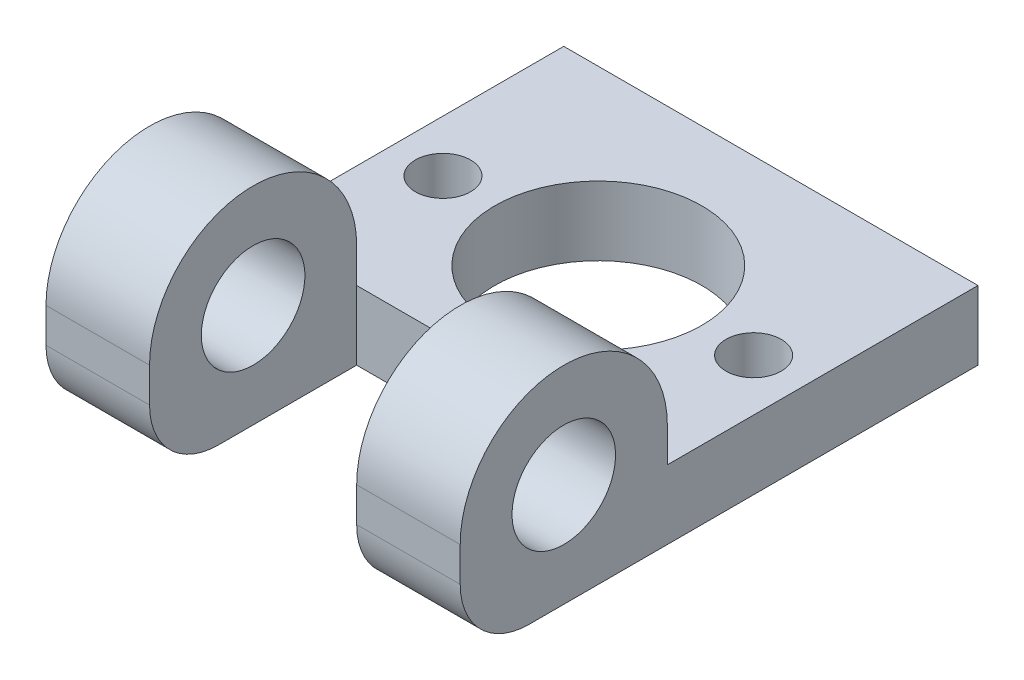
SolidWorks part; units mm, degrees
ref_plane "前视基准面" through (0, 0, 0) normal (0, 0, 1) x (1, 0, 0)
ref_plane "上视基准面" through (0, 0, 0) normal (0, 1, 0) x (1, 0, 0)
ref_plane "右视基准面" through (0, 0, 0) normal (1, 0, 0) x (0, 0, -1)
sketch "草图1" plane through (0, 0, 0) normal (0, 1, 0) x (1, 0, 0)
  line L0 (-4.5, 2.5) -> (4.5, 2.5) construction
  line L1 (6, -7.5) -> (-6, -7.5)
  line L2 (6, -7.5) -> (6, 7.5)
  line L3 (6, 7.5) -> (-6, 7.5)
  line L4 (-6, -7.5) -> (-6, 7.5)
  line L5 (0, 7.5) -> (0, -7.5) construction
  line L6 (6, 0) -> (-6, 0) construction
  line L7 (0, 2.5) -> (0, 7.5) construction
  circle A0 centre (-4.5, 2.5) radius 0.8
  circle A1 centre (4.5, 2.5) radius 0.8
  circle A2 centre (0, 2.5) radius 3
  point P0 (0, 0)
  dimension "D3" = 9
  dimension "D4" = 1.6
  dimension "D5" = 5
  dimension "D6" = 6
  dimension "D1" = 12
  dimension "D2" = 15
extrude "凸台-拉伸1" add sketch "草图1" along normal blind 2
sketch "草图2" plane through (-6, 0, 0) normal (-1, 0, 0) x (0, 0, 1)
  line L1 (1.5, 3) -> (1.5, 2)
  line L2 (-7.5, 2) -> (7.5, 2) construction
  line L3 (7.5, 2) -> (7.5, 3)
  line L4 (-7.5, 0) -> (7.5, 0) construction
  arc A0 (7.5, 3) -> (1.5, 3) centre (4.5, 3) ccw
  circle A1 centre (4.5, 3) radius 1.5
  line M3 (7.5, 2) -> (-7.5, 2)
  dimension "D1" = 1.5
  dimension "D2" = 3
  dimension "D3" = 3
extrude "凸台-拉伸3" add sketch "草图2" against normal up to surface (12 mm away) contours A1 A0 M3 region at (-6, 5.9279, 4.5) up to face at (6, 1, 0)
extrude "切除-拉伸1" cut sketch "草图2<3>" against normal up to next contours A1
sketch "草图2<3>" plane through (-6, 0, 0) normal (-1, 0, 0) x (0, 0, 1) same geometry as "草图2"
ref_plane "基准面1" through (0, 0, 0) normal (-1, 0, 0) x (0, 0, 1)
sketch "草图5" plane through (0, 0, 0) normal (-1, 0, 0) x (0, 0, 1)
  line L0 (1.5, 2) -> (1.5, 0)
  line L4 (-7.5, 0) -> (7.5, 0)
  line L5 (-7.5, 2) -> (-7.5, 0)
  line L6 (1.5, 2) -> (-7.5, 2)
  line L7 (7.5, 0) -> (7.5, 3)
  line L8 (1.5, 0) -> (7.5, 0)
  line L11 (7.5, 0) -> (7.5, 3)
  line L12 (1.5, 3) -> (1.5, 2)
  line L13 (1.5, 3) -> (1.5, 2)
  arc A1 (7.5, 3) -> (1.5, 3) centre (4.5, 3) ccw
  arc A2 (7.5, 3) -> (1.5, 3) centre (4.5, 3) ccw
  dimension "D1" = 0
extrude "切除-拉伸2" cut sketch "草图5" against normal blind 3 and the other way blind 3
fillet "圆角1" radius 2 2 edges at (4.5, 0, 7.5) (-4.5, 0, 7.5)
